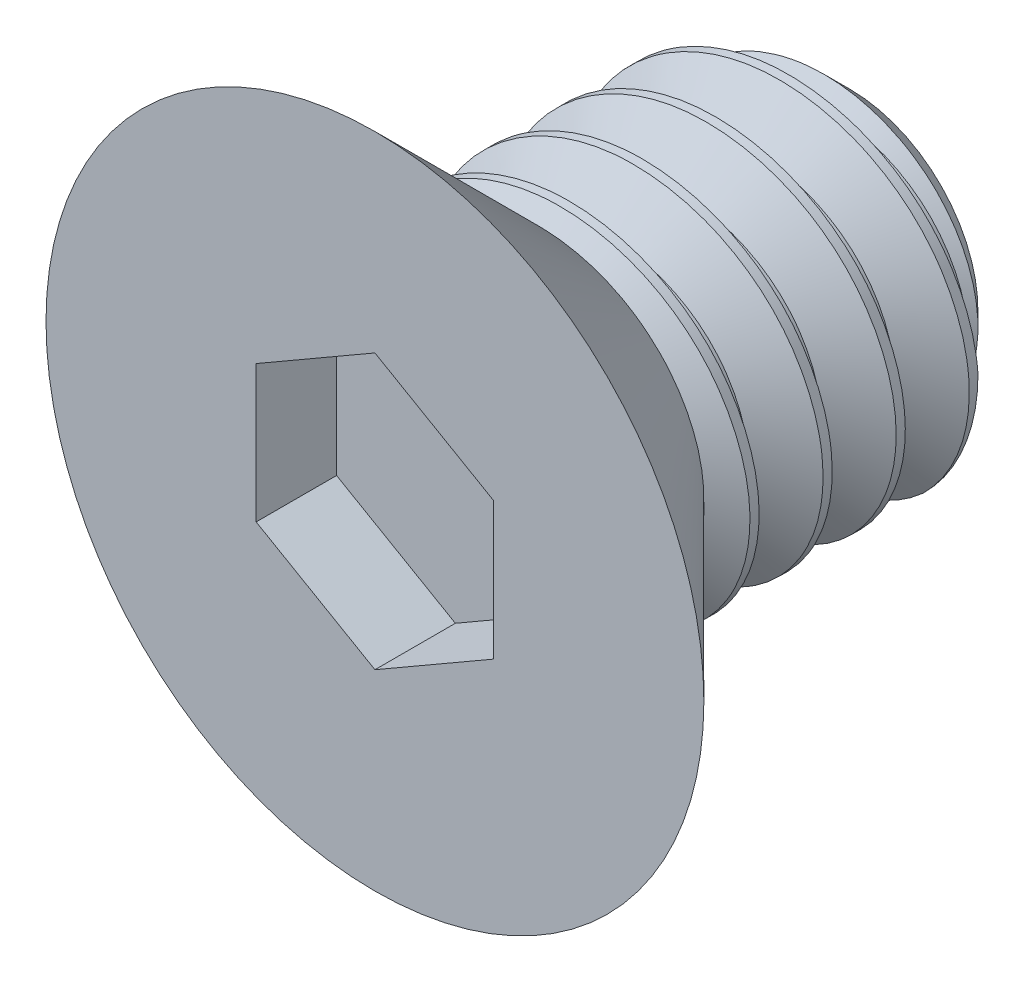
SolidWorks part; units mm, degrees
ref_plane "Front" through (0, 0, 0) normal (0, 0, 1) x (1, 0, 0)
ref_plane "Top" through (0, 0, 0) normal (0, 1, 0) x (1, 0, 0)
ref_plane "Right" through (0, 0, 0) normal (1, 0, 0) x (0, 0, -1)
sketch "Sketch1" plane through (0, 0, 0) normal (1, 0, 0) x (0, 0, -1)
  line L0 (0, 2) -> (0.2, 2) construction
  line L1 (0.2, 2) -> (1.2, 1) construction
  line L2 (0, 1) -> (3, 1)
  line L3 (3, 1) -> (3, 0)
  line L4 (3, 0) -> (0, 0)
  line L5 (0, 0) -> (0, 2) construction
  line L6 (0, 2) -> (0, -2) construction
  line L7 (3, 1) -> (3, -1) construction
  line L8 (0, -2) -> (0.2, -2) construction
  line L9 (0.2, -2) -> (1.2, -1) construction
  line L11 (0, 1) -> (0, 0)
  line L12 (1.2, 1) -> (1.2, 0) construction
revolve "Revolve1" add sketch "Sketch1" angle 360 mid plane about L4
sketch "Sketch3" plane through (0, 0, -3) normal (0, 0, -1) x (-1, 0, 0)
  circle A0 centre (0, 0) radius 1
curve "Helix/Spiral1" pitch 0.4 height 3 radius 1 centre (0, 0, -3) axis (0, 0, 1) start towards (0, 1, 0)
sketch "Sketch2" plane through (0, 0, 0) normal (1, 0, 0) x (0, 0, -1)
  line L0 (3, 1) -> (3.35, 1)
  line L1 (3.35, 1) -> (3.2, 0.7402)
  line L2 (3.2, 0.7402) -> (3.15, 0.7402)
  line L3 (3.15, 0.7402) -> (3, 1)
  line L4 (3.075, 0.8701) -> (3.275, 0.8701) construction
  dimension "D1" = 60
  dimension "D2" = 0.05
  dimension "D3" = 0.2
chamfer "Chamfer1" distance 0.3 angle 45 1 edges at (0, 1, -3)
sweep "Cut-Sweep1" cut profiles "Sketch2" path "Helix/Spiral1" align with end faces yes
sketch "Sketch7" plane through (0, 0, 0) normal (1, 0, 0) x (0, 0, -1)
  line L0 (0, 2) -> (0.2, 2) construction
  line L1 (0.2, 2) -> (1.2, 1) construction
  line L2 (0, 2) -> (0.2, 2)
  line L3 (0.2, 2) -> (1.2, 1)
  line L4 (1.2, 1) -> (1.2, 0) construction
  line L5 (1.2, 1) -> (1.2, 0)
  line L7 (0, 0) -> (0, 2) construction
  line L8 (0, 0) -> (0, 2)
  line L9 (0, 0) -> (1.2, 0)
  line L10 (2.2, 0) -> (-2.2, 0) construction
revolve "Revolve2" add sketch "Sketch7" angle 360 mid plane about L9
ref_plane "Plane1" through (0, 0, -1.2) normal (0, 0, 1) x (1, 0, 0)
sketch "Sketch8" plane through (0, 0, -1.2) normal (0, 0, 1) x (1, 0, 0)
  circle A0 centre (0, 0) radius 1
extrude "Boss-Extrude1" add sketch "Sketch8" against normal through all draft 45
sketch "Sketch5" plane through (0, 0, 0) normal (0, 0, 1) x (1, 0, 0)
  line L1 (0.65, -0.3753) -> (0.65, 0.3753)
  line L2 (0.65, 0.3753) -> (0, 0.7506)
  line L3 (0, 0.7506) -> (-0.65, 0.3753)
  line L4 (-0.65, 0.3753) -> (-0.65, -0.3753)
  line L5 (-0.65, -0.3753) -> (0, -0.7506)
  line L6 (0, -0.7506) -> (0.65, -0.3753)
  circle A0 centre (0, 0) radius 0.65 construction
  dimension "Hex" = 1.3
extrude "Cut-Extrude2" cut sketch "Sketch5" against normal blind 0.84
sketch "Sketch6" plane through (0, 0, 0) normal (0, 0, 1) x (1, 0, 0)
  circle A0 centre (0, 0) radius 0.7506
extrude "Cut-Extrude3" cut sketch "Sketch6" against normal blind 0.84 draft 45
sketch "Sketch9" [suppressed] plane through (0, 0, -5.5) normal (0, 0, 1) x (1, 0, 0)
  circle A1 centre (0, 0) radius 5
  circle A2 centre (0, 0) radius 5
  point P0 (0, 5)
  dimension "D1" = 0
extrude "Boss-Extrude2" [suppressed] add sketch "Sketch9" against normal offset from surface (18.5 mm away) 26 up to face at (0, 0.7, -3)
fillet "Fillet1" [suppressed] radius 0.2
sketch "Sketch10" plane through (0, 0, 0) normal (1, 0, 0) x (0, 0, -1)
  line L0 (3, 1) -> (3, -1) construction
  point P0 (2.4, -1)
  dimension "D1" = 0.6
sketch "Sketch11" plane through (0, 0, 0) normal (1, 0, 0) x (0, 0, -1)
  line L0 (3, 0) -> (0, 0) construction
  line L1 (0.4, 0) -> (0, 0)
  line L2 (0.4, 0) -> (0.4, 2)
  line L3 (0.4, 2) -> (0, 2)
  line L4 (0, 0) -> (0, 2)
  dimension "D1" = 2.6
revolve "Cut-Revolve1" cut sketch "Sketch11" angle 360 about L4
equation "\"D3@Helix/Spiral1\" = \"Lg@Sketch1\""
equation "\"D2@Sketch2\" = \"D4@Helix/Spiral1\" * .125"
equation "\"D3@Sketch2\" = \"D4@Helix/Spiral1\" * .5"
equation "\"D1@Chamfer1\" = \"D4@Helix/Spiral1\" * .75"
equation "\"D1@Cut-Extrude2\" = \"Head Ht@Sketch1\" * .7"
equation "\"D1@Sketch10\" = \"D4@Helix/Spiral1\" * 1.5"
equation "\"D1@Cut-Extrude3\" = \"D1@Cut-Extrude2\""
equation "\"D1@Fillet1\" = \"Dia@Sketch1\" * .1"
